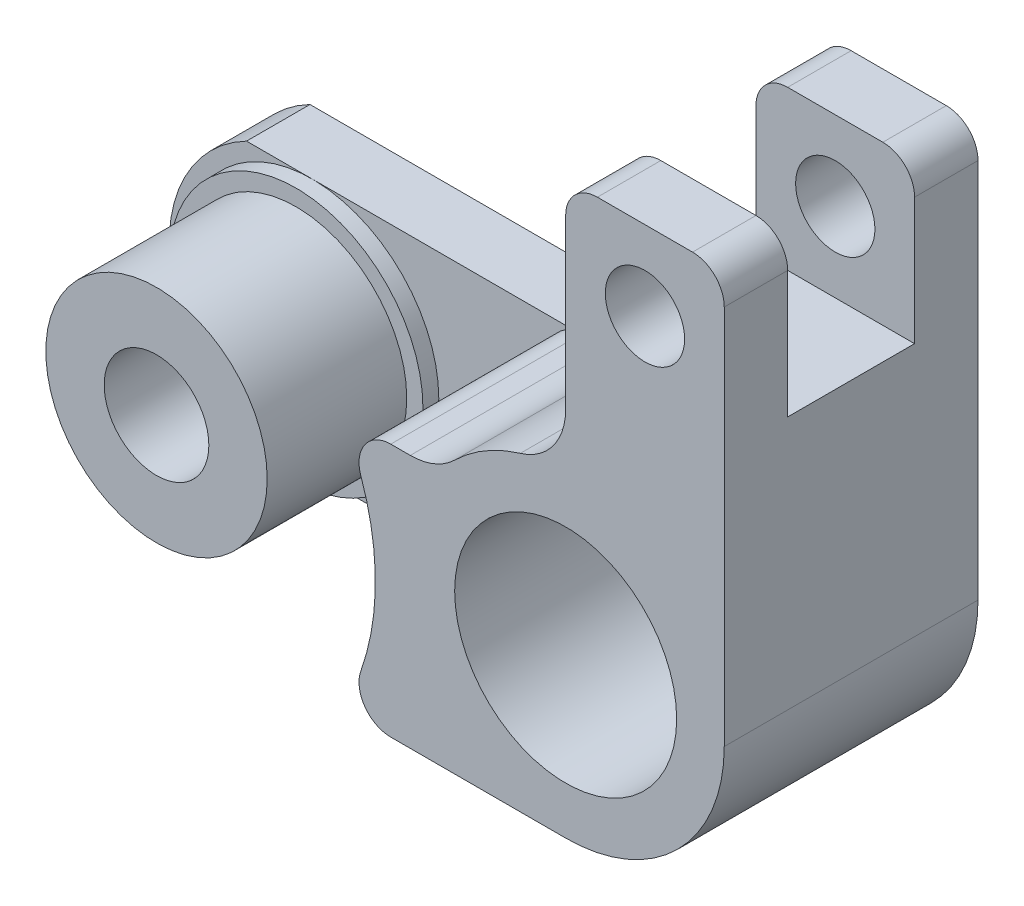
SolidWorks part; units mm, degrees
ref_plane "Plan de face" through (0, 0, 0) normal (0, 0, 1) x (1, 0, 0)
ref_plane "Plan de dessus" through (0, 0, 0) normal (0, 1, 0) x (1, 0, 0)
ref_plane "Plan de droite" through (0, 0, 0) normal (1, 0, 0) x (0, 0, -1)
sketch "Esquisse1" plane through (0, 0, 0) normal (0, 0, 1) x (1, 0, 0)
  line L0 (0, 0) -> (24, 0)
  line L1 (24, 0) -> (24, 18)
  line L2 (24, 18) -> (19, 18)
  line L3 (19, 18) -> (19, 8)
  line L4 (19, 8) -> (0, 8)
  line L5 (0, 8) -> (0, 0)
  dimension "D1" = 8
  dimension "D2" = 5
  dimension "D3" = 24
  dimension "D4" = 18
extrude "Boss.-Extru.1" add sketch "Esquisse1" along normal blind 8
sketch "Esquisse2" plane through (0, 0, 8) normal (0, 0, 1) x (1, 0, 0)
  line L0 (0, 0) -> (24, 0) construction
  line L1 (24, 0) -> (24, 18) construction
  circle A0 centre (19, 5) radius 5
  dimension "D3" = 10
  dimension "D1" = 5
  dimension "D2" = 5
extrude "Boss.-Extru.2" add sketch "Esquisse2" against normal up to vertex (8 mm away) up to point (19, 8, 0)
sketch "Esquisse3" plane through (0, 0, 8) normal (0, 0, 1) x (1, 0, 0)
  circle A0 centre (19, 5) radius 3.5
  arc A1 (19, 10) -> (15, 8) centre (19, 5) ccw construction
  dimension "D1" = 7
extrude "Enlèv. mat.-Extru.1" cut sketch "Esquisse3" against normal blind 7
sketch "Esquisse4" plane through (0, 0, 1) normal (0, 0, 1) x (1, 0, 0)
  circle A0 centre (19, 5) radius 2.5
  dimension "D1" = 5
extrude "Enlèv. mat.-Extru.2" cut sketch "Esquisse4" against normal through all both and the other way through all
sketch "Esquisse5" plane through (0, 0, 8) normal (0, 0, 1) x (1, 0, 0)
  line L0 (0, 0) -> (24, 0) construction
  line L1 (0, 8) -> (0, 0) construction
  circle A0 centre (5, 4) radius 8
  dimension "D2" = 5
  dimension "D3" = 16
  dimension "D1" = 4
extrude "Enlèv. mat.-Extru.3" cut sketch "Esquisse5" against normal blind 6
sketch "Esquisse6" plane through (0, 0, 2) normal (0, 0, 1) x (1, 0, 0)
  circle A0 centre (5, 4) radius 3.49
  arc A1 (11.9282, 0) -> (11.9282, 8) centre (5, 4) ccw construction
  dimension "D1" = 6.98
extrude "Boss.-Extru.3" add sketch "Esquisse6" along normal blind 4.9
sketch "Esquisse7" plane through (0, 0, 6.9) normal (0, 0, 1) x (1, 0, 0)
  circle A0 centre (5, 4) radius 1.65
  dimension "D1" = 3.3
extrude "Enlèv. mat.-Extru.4" cut sketch "Esquisse7" against normal through all both and the other way through all
sketch "Esquisse8" plane through (0, 0, 2) normal (0, 0, 1) x (1, 0, 0)
  line L1 (0, 8) -> (2.9384, 8)
  line L2 (0, 0) -> (2.9384, 0)
  line L3 (0, 0) -> (0, 8)
  circle A1 centre (5, 4) radius 4.5 construction
  arc A2 (2.9384, 0) -> (2.9384, 8) centre (5, 4) cw
  dimension "D1" = 9
extrude "Enlèv. mat.-Extru.5" cut sketch "Esquisse8" against normal through all both and the other way through all
fillet "Congé1" radius 5 1 edges at (24, 0, 4)
fillet "Congé2" radius 1 4 edges at (11.9282, 8, 5) (11.9282, 0, 5) (24, 18, 4) (19, 18, 4)
sketch "Esquisse9" plane through (0, 18, 0) normal (0, 1, 0) x (1, 0, 0)
  line L0 (20, -4) -> (23, -4) construction
  line L1 (20, 0) -> (20, -8) construction
  line L2 (23, -8) -> (23, 0) construction
  line L3 (21.5, -6) -> (21.5, -2) construction
  line L4 (19, -2) -> (24, -2)
  line L5 (24, 0) -> (24, -8) construction
  line L6 (24, -2) -> (24, -6)
  line L7 (19, -2) -> (19, -6)
  line L8 (19, -6) -> (24, -6)
  point P15 (21.5, -4)
  point P16 (19, -4)
  point P17 (24, -4)
  dimension "D1" = 4
extrude "Enlèv. mat.-Extru.6" cut sketch "Esquisse9" against normal blind 5
fillet "Congé3" radius 2 2 edges at (19, 10, 4) (15, 8, 4)
sketch "Esquisse10" plane through (0, 0, 8) normal (0, 0, 1) x (1, 0, 0)
  line L0 (21.5, 18) -> (21.5, 15.5) construction
  line L1 (23, 18) -> (20, 18) construction
  circle A0 centre (21.5, 15.5) radius 1.25
  dimension "D1" = 2.5
  dimension "D2" = 2.5
extrude "Enlèv. mat.-Extru.7" cut sketch "Esquisse10" against normal through all both and the other way through all
sketch "Esquisse11" plane through (0, 0, 6.9) normal (0, 0, 1) x (1, 0, 0)
  circle A1 centre (5, 4) radius 3.49
  circle A2 centre (5, 4) radius 4
  dimension "D1" = 6.98
  dimension "D2" = 8
extrude "Boss.-Extru.4" add sketch "Esquisse11" along normal blind 0.5 from surface separate body starting at face at (9.2102, 4, 2)
